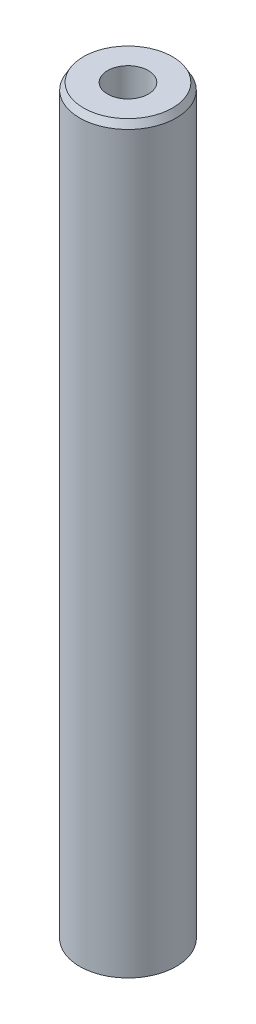
SolidWorks part; units mm, degrees
ref_plane "Front Plane" through (0, 0, 0) normal (0, 0, 1) x (1, 0, 0)
ref_plane "Top Plane" through (0, 0, 0) normal (0, 1, 0) x (1, 0, 0)
ref_plane "Right Plane" through (0, 0, 0) normal (1, 0, 0) x (0, 0, -1)
sketch "Sketch1" plane through (0, 0, 0) normal (0, 1, 0) x (1, 0, 0)
  circle A0 centre (0, 0) radius 7.5
  dimension "SHAFT_OD" = 15
extrude "Boss-Extrude1" add sketch "Sketch1" along normal blind 115.6413
sketch "Sketch2" plane through (0, 0, 0) normal (0, 1, 0) x (1, 0, 0)
  circle A0 centre (0, 0) radius 3.1659
  dimension "BORE_D" = 6.3318
extrude "Cut-Extrude1" cut sketch "Sketch2" along normal through all
chamfer "Chamfer1" distance 1.0358 angle 30 2 edges at (0, 115.6413, 7.5) (0, 0, 7.5) first distance on face at (0, 115.6413, 7.5) first distance on face at (0, 0, 3.1659)
